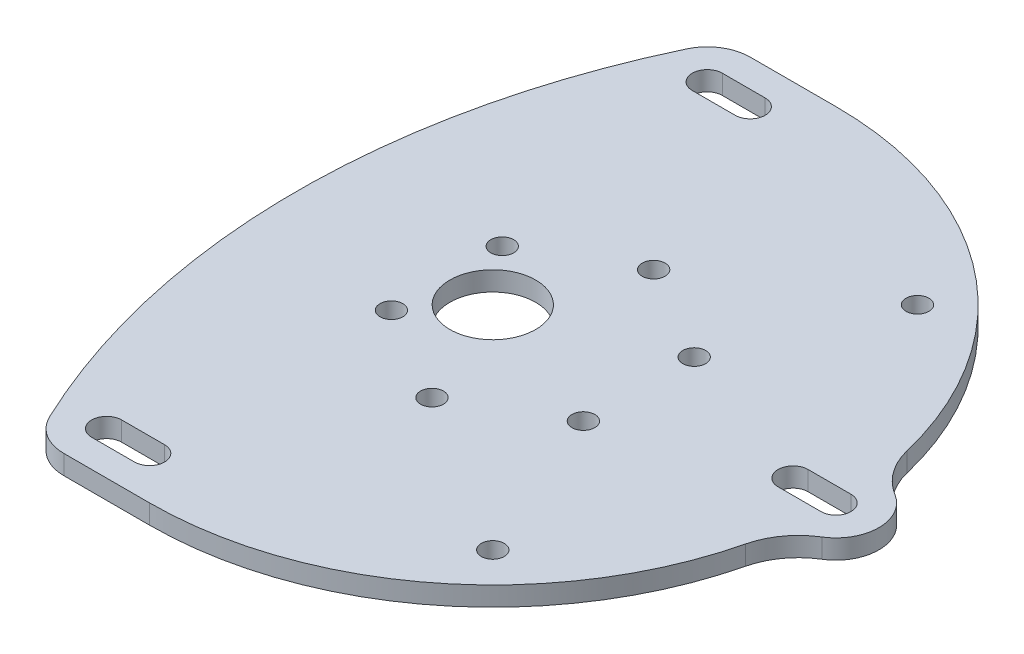
SolidWorks part; units mm, degrees
ref_plane "Plan de face" through (0, 0, 0) normal (0, 0, 1) x (1, 0, 0)
ref_plane "Plan de dessus" through (0, 0, 0) normal (0, 1, 0) x (1, 0, 0)
ref_plane "Plan de droite" through (0, 0, 0) normal (1, 0, 0) x (0, 0, -1)
sketch "Esquisse1" plane through (0, 0, 0) normal (0, 1, 0) x (1, 0, 0)
  line L0 (-5, 42) -> (-17, 42) construction
  line L1 (-5, -42) -> (-17, -42) construction
  line L2 (37, 0) -> (43, 0) construction
  line L3 (-17, 48) -> (-5, 48) construction
  line L4 (-17, 36) -> (-5, 36) construction
  line L5 (-17, -36) -> (-5, -36) construction
  line L6 (-17, -48) -> (-5, -48) construction
  line L7 (-17, 42) -> (-11, 42) construction
  line L8 (-17, 44.1) -> (-11, 44.1) construction
  line L9 (-17, 39.9) -> (-11, 39.9) construction
  line L10 (43, 0) -> (37, 0) construction
  line L11 (43, -2.1) -> (37, -2.1) construction
  line L12 (43, 2.1) -> (37, 2.1) construction
  line L13 (-17, -42) -> (-11, -42) construction
  line L14 (-17, -39.9) -> (-11, -39.9) construction
  line L15 (-17, -44.1) -> (-11, -44.1) construction
  line L16 (2, 0) -> (2, 15.5) construction
  line L17 (-5, 0) -> (71.5, 0) construction
  arc A0 (-5, -36) -> (-5, 36) centre (-5, 0) ccw construction
  arc A1 (-5, -42) -> (-5, 42) centre (-5, 0) ccw construction
  arc A2 (-5, -48) -> (41.6552, -11.2825) centre (-5, 0) ccw construction
  arc A3 (-17, 48) -> (-17, 36) centre (-17, 42) ccw construction
  arc A4 (-17, -36) -> (-17, -48) centre (-17, -42) ccw construction
  arc A5 (46.1406, -5.1124) -> (46.1406, 5.1124) centre (43, 0) ccw construction
  arc A6 (41.6552, -11.2825) -> (46.1406, -5.1124) centre (51.375, -13.633) cw construction
  arc A7 (46.1406, 5.1124) -> (41.6552, 11.2825) centre (51.375, 13.633) cw construction
  arc A8 (41.6552, 11.2825) -> (-5, 48) centre (-5, 0) ccw construction
  arc A9 (-17, 44.1) -> (-17, 39.9) centre (-17, 42) ccw construction
  arc A10 (-11, 39.9) -> (-11, 44.1) centre (-11, 42) ccw construction
  arc A11 (43, -2.1) -> (43, 2.1) centre (43, 0) ccw construction
  arc A12 (37, 2.1) -> (37, -2.1) centre (37, 0) ccw construction
  arc A13 (-17, -39.9) -> (-17, -44.1) centre (-17, -42) ccw construction
  arc A14 (-11, -44.1) -> (-11, -39.9) centre (-11, -42) ccw construction
  circle A15 centre (-5, 0) radius 33.75 construction
  circle A16 centre (-5, 0) radius 6 construction
  circle A17 centre (2, 0) radius 18.5 construction
  circle A18 centre (2, 15.5) radius 1.6 construction
  circle A19 centre (-5, 0) radius 32.25 construction
  arc A20 (-20.3996, 58.1465) -> (-22.5386, -54.6197) centre (71.5, 0) ccw construction
  arc A22 (-19.2555, 56.6784) -> (-22.0691, -51.902) centre (71.5, 0) ccw construction
  point P23 (-14, 42)
  point P29 (40, 0)
  point P34 (-14, -42)
  dimension "D2" = 67.5
  dimension "D3" = 12
  dimension "D4" = 6
  dimension "D9" = 2.1
  dimension "D10" = 2.1
  dimension "D12" = 2.1
  dimension "D13" = 12
  dimension "D15" = 37
  dimension "D17" = 3.2
  dimension "D18" = 64.5
  dimension "D19" = 108.75
  dimension "D20" = 107
  dimension "D21" = 42
  dimension "D5" = 12
  dimension "D7" = 12
  dimension "D8" = 6
  dimension "D11" = 6
  dimension "D14" = 7
  dimension "D16" = 15.5
sketch "Esquisse2" plane through (0, 0, 0) normal (0, 1, 0) x (1, 0, 0)
  line L8 (-17, -48) -> (-5, -48) construction
  line L10 (-17, 44.1) -> (-11, 44.1) construction
  line L11 (-17, 48) -> (-5, 48) construction
  line L13 (-17, 44.1) -> (-11, 44.1)
  line L14 (-17, 39.9) -> (-11, 39.9) construction
  line L15 (-17, 39.9) -> (-11, 39.9)
  line L16 (43, 2.1) -> (37, 2.1) construction
  line L17 (43, -2.1) -> (37, -2.1) construction
  line L18 (43, 2.1) -> (37, 2.1)
  line L19 (43, -2.1) -> (37, -2.1)
  line L20 (-17, -44.1) -> (-11, -44.1) construction
  line L21 (-17, -39.9) -> (-11, -39.9) construction
  line L22 (-17, -44.1) -> (-11, -44.1)
  line L23 (-17, -39.9) -> (-11, -39.9)
  line L24 (-17, -48) -> (-5, -48)
  line L25 (-17, 48) -> (-5, 48)
  line L26 (-5, 0) -> (24.6985, 29.6985) construction
  line L27 (-5, 0) -> (24.6985, -29.6985) construction
  line L28 (-5, 0) -> (71.5, 0) construction
  arc A0 (-22.4206, 44.5725) -> (-22.4206, -44.5725) centre (71.5, 0) ccw
  arc A1 (-17, 48) -> (-17, 36) centre (-17, 42) ccw construction
  arc A10 (-17, -36) -> (-17, -48) centre (-17, -42) ccw construction
  circle A12 centre (-5, 0) radius 6 construction
  circle A13 centre (-5, 0) radius 6
  arc A15 (-17, 44.1) -> (-17, 39.9) centre (-17, 42) ccw construction
  arc A16 (-17, 44.1) -> (-17, 39.9) centre (-17, 42) ccw
  arc A17 (-11, 39.9) -> (-11, 44.1) centre (-11, 42) ccw construction
  arc A18 (-11, 39.9) -> (-11, 44.1) centre (-11, 42) ccw
  arc A19 (43, -2.1) -> (43, 2.1) centre (43, 0) ccw construction
  arc A20 (37, 2.1) -> (37, -2.1) centre (37, 0) ccw construction
  arc A21 (43, -2.1) -> (43, 2.1) centre (43, 0) ccw
  arc A22 (37, 2.1) -> (37, -2.1) centre (37, 0) ccw
  arc A23 (-17, -39.9) -> (-17, -44.1) centre (-17, -42) ccw construction
  arc A24 (-11, -44.1) -> (-11, -39.9) centre (-11, -42) ccw construction
  arc A25 (-17, -39.9) -> (-17, -44.1) centre (-17, -42) ccw
  arc A26 (-11, -44.1) -> (-11, -39.9) centre (-11, -42) ccw
  arc A34 (-5, -48) -> (41.6552, -11.2825) centre (-5, 0) ccw construction
  arc A35 (46.1406, -5.1124) -> (41.6552, -11.2825) centre (51.375, -13.633) ccw construction
  arc A36 (46.1406, -5.1124) -> (46.1406, 5.1124) centre (43, 0) ccw construction
  arc A37 (41.6552, 11.2825) -> (46.1406, 5.1124) centre (51.375, 13.633) ccw construction
  arc A38 (41.6552, 11.2825) -> (-5, 48) centre (-5, 0) ccw construction
  arc A39 (-17, 48) -> (-22.4206, 44.5725) centre (-17, 42) ccw
  arc A40 (-22.4206, -44.5725) -> (-17, -48) centre (-17, -42) ccw
  arc A41 (-5, -48) -> (41.6552, -11.2825) centre (-5, 0) ccw
  arc A42 (46.1406, -5.1124) -> (41.6552, -11.2825) centre (51.375, -13.633) ccw
  arc A43 (46.1406, -5.1124) -> (46.1406, 5.1124) centre (43, 0) ccw
  arc A44 (41.6552, 11.2825) -> (46.1406, 5.1124) centre (51.375, 13.633) ccw
  arc A45 (41.6552, 11.2825) -> (-5, 48) centre (-5, 0) ccw
  arc A46 (-5, -42) -> (-5, 42) centre (-5, 0) ccw construction
  circle A47 centre (24.6985, 29.6985) radius 1.6
  circle A48 centre (24.6985, -29.6985) radius 1.6
  point P45 (42.5109, 6.835)
  point P54 (-5, -0.5591)
  dimension "D2" = 3.2
  dimension "D1" = 45
extrude "Boss.-Extru.1" add sketch "Esquisse2" along normal blind 2.7
sketch "Esquisse3" plane through (0, 0, 0) normal (0, 1, 0) x (1, 0, 0)
  circle A0 centre (2, 15.5) radius 1.6 construction
  circle A1 centre (2, 15.5) radius 1.6
extrude "Enlèv. mat.-Extru.1" cut sketch "Esquisse3" along normal through all
ref_axis "Axe1" through (2, 0, 0) along (0, 1, 0)
pattern_circular "Répétition circulaire1" count 6 over 360 about axis through (2, 0, 0) along (0, 1, 0) of "Enlèv. mat.-Extru.1"
ref_axis "Axe2" through (71.5, 0, 0) along (0, 1, 0)
ref_axis "Axe3" through (-14, 0, -42) along (0, 1, 0)
ref_axis "Axe4" through (-14, 0, 42) along (0, 1, 0)
